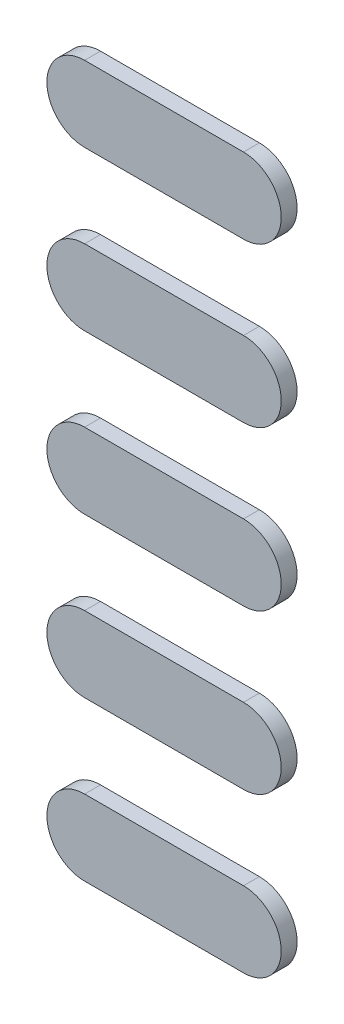
SolidWorks part; units mm, degrees
ref_plane "Front Plane" through (0, 0, 0) normal (0, 0, 1) x (1, 0, 0)
ref_plane "Top Plane" through (0, 0, 0) normal (0, 1, 0) x (1, 0, 0)
ref_plane "Right Plane" through (0, 0, 0) normal (1, 0, 0) x (0, 0, -1)
sketch "Sketch1" plane through (0, 0, 0) normal (0, 0, 1) x (1, 0, 0)
  line L0 (10, 0) -> (-10, 0) construction
  line L1 (10, -4.75) -> (-10, -4.75)
  line L2 (10, 4.75) -> (-10, 4.75)
  line L3 (0, 5) -> (-10, 5) construction
  line L4 (10, 20) -> (-10, 20) construction
  line L5 (10, 15.25) -> (-10, 15.25)
  line L6 (10, 24.75) -> (-10, 24.75)
  line L7 (10, 40) -> (-10, 40) construction
  line L8 (10, 35.25) -> (-10, 35.25)
  line L9 (10, 44.75) -> (-10, 44.75)
  line L10 (10, -20) -> (-10, -20) construction
  line L11 (10, -24.75) -> (-10, -24.75)
  line L12 (10, -15.25) -> (-10, -15.25)
  line L13 (10, -40) -> (-10, -40) construction
  line L14 (10, -44.75) -> (-10, -44.75)
  line L15 (10, -35.25) -> (-10, -35.25)
  arc A0 (10, -4.75) -> (10, 4.75) centre (10, 0) ccw
  arc A1 (-10, 4.75) -> (-10, -4.75) centre (-10, 0) ccw
  arc A4 (10, -5) -> (10, 5) centre (10, 0) ccw construction
  arc A5 (10, 15.25) -> (10, 24.75) centre (10, 20) ccw
  arc A6 (-10, 24.75) -> (-10, 15.25) centre (-10, 20) ccw
  arc A7 (10, 35.25) -> (10, 44.75) centre (10, 40) ccw
  arc A8 (-10, 44.75) -> (-10, 35.25) centre (-10, 40) ccw
  arc A9 (10, -24.75) -> (10, -15.25) centre (10, -20) ccw
  arc A10 (-10, -15.25) -> (-10, -24.75) centre (-10, -20) ccw
  arc A11 (10, -44.75) -> (10, -35.25) centre (10, -40) ccw
  arc A12 (-10, -35.25) -> (-10, -44.75) centre (-10, -40) ccw
  point P2 (0, 0)
  point P10 (14.75, 0)
  point P14 (15, 0)
  point P19 (0, 20)
  point P26 (0, 40)
  point P33 (0, -20)
  point P40 (0, -40)
  dimension "D2" = 0.25
  dimension "D1" = 0.25
  dimension "D3" = 3
  dimension "D4" = 20
  dimension "D6" = 20
  dimension "D5" = 3
extrude "Boss-Extrude1" add sketch "Sketch1" along normal blind 2
